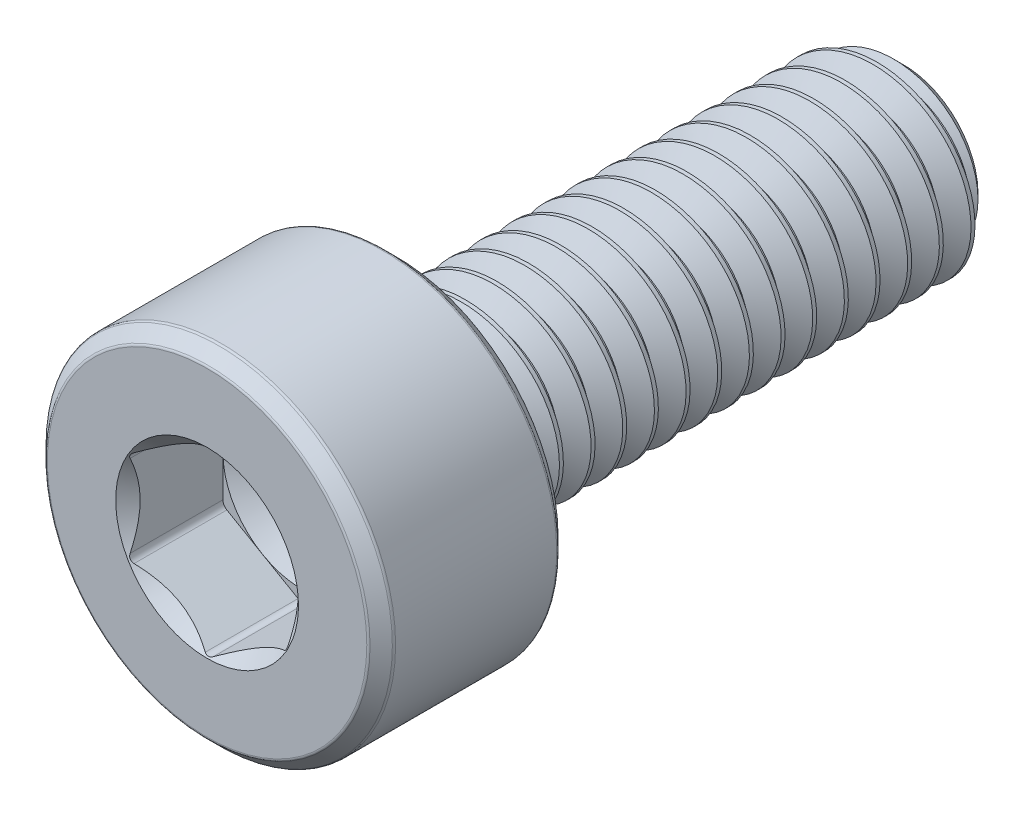
SolidWorks part; units mm, degrees
material "AISI 316 Stainless Steel Sheet (SS)"
ref_plane "Front Plane" through (0, 0, 0) normal (0, 0, 1) x (1, 0, 0)
ref_plane "Top Plane" through (0, 0, 0) normal (0, 1, 0) x (1, 0, 0)
ref_plane "Right Plane" through (0, 0, 0) normal (1, 0, 0) x (0, 0, -1)
sketch "Sketch1" plane through (0, 0, 0) normal (1, 0, 0) x (0, 0, -1)
  line L0 (-5.5, 0) -> (5.5, 0) construction
  line L1 (-5.5, 0) -> (-5.5, 2.75)
  line L2 (-5.5, 2.75) -> (-2.5, 2.75)
  line L3 (-2.5, 2.75) -> (-2.5, 1.5)
  line L4 (-2.5, 1.5) -> (5.1752, 1.5)
  line L5 (5.4687, 1.5541) -> (5.7187, 1.1211) construction
  line L6 (5.7187, 1.1211) -> (5.9687, 1.5541) construction
  line L7 (5.9687, 1.5541) -> (5.4687, 1.5541) construction
  line L8 (5.1752, 1.5) -> (5.5, 1.1752)
  line L9 (5.5, 1.1752) -> (5.5, 0)
  line L10 (5.5, 1.5) -> (5.9375, 1.5) construction
  line L11 (5.7187, 1.5541) -> (5.7187, 1.5) construction
  line L12 (5.7187, 1.5) -> (5.7187, 1.1752) construction
  line L13 (5.7187, 1.1752) -> (5.7187, 1.1211) construction
  line L14 (5.6875, 1.1752) -> (5.75, 1.1752)
  line L15 (5.4844, 1.5271) -> (5.9531, 1.5271)
  line L16 (5.75, 1.1752) -> (5.9531, 1.5271)
  line L17 (5.6875, 1.1752) -> (5.4844, 1.5271)
  line L18 (-5.5, 1.25) -> (-4, 1.25)
  line L19 (-4, 1.25) -> (-4, 0)
  line L20 (3.75, 1.5) -> (3.75, -1.5) construction
  point P20 (5.7187, 1.5271)
  point P22 (3.75, -1.5)
  point P28 (3.75, 0)
  point P29 (5.1752, -1.5)
  dimension "Head Diameter" = 5.5
  dimension "Length" = 8
  dimension "Head Height" = 3
  dimension "Thread Size" = 3
  dimension "D1" = 45
  dimension "Thread Pitch" = 0.5
  dimension "D3" = 0.0625
  dimension "Drive Size" = 2.5
  dimension "D4" = 1.75
  dimension "D5" = 1.5
sketch "Sketch3" plane through (0, 0, 0) normal (1, 0, 0) x (0, 0, -1)
  line L0 (-5.5, 2.5224) -> (-5.5, 1.25)
  line L1 (-5.5, 1.25) -> (-4, 1.25)
  line L2 (-4, 1.25) -> (-4, 0)
  line L3 (-4, 0) -> (5.5, 0)
  line L4 (5.5, 0) -> (5.5, 1.1752)
  line L5 (5.5, 1.1752) -> (5.1752, 1.5)
  line L6 (5.1752, 1.5) -> (-2.5, 1.5)
  line L7 (-2.5, 1.5) -> (-2.5, 2.5224)
  line L8 (-2.7276, 2.75) -> (-5.2724, 2.75)
  line L9 (-5.4849, 2.5589) -> (-5.3089, 2.7349)
  line L11 (-5.5, 2.75) -> (-2.5, 2.75) construction
  line L12 (-2.6911, 2.7349) -> (-2.5151, 2.5589)
  arc A5 (-2.5151, 2.5589) -> (-2.5, 2.5224) centre (-2.5516, 2.5224) cw
  arc A6 (-2.7276, 2.75) -> (-2.6911, 2.7349) centre (-2.7276, 2.6984) cw
  arc A7 (-5.2724, 2.75) -> (-5.3089, 2.7349) centre (-5.2724, 2.6984) ccw
  arc A8 (-5.5, 2.5224) -> (-5.4849, 2.5589) centre (-5.4484, 2.5224) cw
  point P17 (-4, 2.75)
  point P29 (-5.5, 2.5438)
  dimension "D3" = 0.0516
  dimension "D1" = 45
  dimension "D2" = 0.2062
revolve "Revolve1" add sketch "Sketch3" angle 360 about L0
sketch "Sketch4" plane through (0, 0, 5.5) normal (0, 0, 1) x (1, 0, 0)
  line L1 (0, 1.4434) -> (-1.25, 0.7217)
  line L2 (-1.25, 0.7217) -> (-1.25, -0.7217)
  line L3 (-1.25, -0.7217) -> (0, -1.4434)
  line L4 (0, -1.4434) -> (1.25, -0.7217)
  line L5 (1.25, -0.7217) -> (1.25, 0.7217)
  line L6 (1.25, 0.7217) -> (0, 1.4434)
  circle A0 centre (0, 0) radius 1.25 construction
extrude "Cut-Extrude1" cut sketch "Sketch4" against normal up to vertex (1.5 mm away) up to point (0, 1.25, 4)
sketch "Sketch5" plane through (0, 0, 5.5) normal (0, 0, 1) x (1, 0, 0)
  circle A0 centre (0, 0) radius 1.4434
extrude "Cut-Extrude2" cut sketch "Sketch5" against normal up to next (1.5 mm away) draft 45
sketch "Sketch10" plane through (0, 0, 4) normal (0, 0, 1) x (1, 0, 0)
  line L0 (1.25, 0.7217) -> (1.25, -0.7217) construction
  circle A0 centre (0, 0) radius 1.25
extrude "Cut-Extrude3" cut sketch "Sketch10" against normal through all draft 60
fillet "Fillet1" radius 0.125 6 edges at (-1.25, 0.7217, 4.75) (0, 1.4434, 4.75) (1.25, 0.7217, 4.75) (1.25, -0.7217, 4.75) (0, -1.4434, 4.75) (-1.25, -0.7217, 4.75)
sketch "Sketch6" plane through (0, 0, -5.5) normal (0, 0, -1) x (-1, 0, 0)
  circle A0 centre (0, 0) radius 1.5 construction
  circle A1 centre (0, 0) radius 1.5
curve "Helix/Spiral1" pitch 0.5 height 8.5 radius 1.5 centre (0, 0, -5.5) axis (0, 0, 1) start towards (0, 1, 0)
sketch "Sketch7" plane through (0, 0, 0) normal (1, 0, 0) x (0, 0, -1)
  line L0 (5.6875, 1.1752) -> (5.75, 1.1752) construction
  line L1 (5.6875, 1.1752) -> (5.4844, 1.5271) construction
  line L2 (5.4844, 1.5271) -> (5.9531, 1.5271) construction
  line L3 (5.75, 1.1752) -> (5.9531, 1.5271) construction
  line L4 (5.6875, 1.1752) -> (5.75, 1.1752)
  line L5 (5.6875, 1.1752) -> (5.4844, 1.5271)
  line L6 (5.4844, 1.5271) -> (5.9531, 1.5271)
  line L7 (5.75, 1.1752) -> (5.9531, 1.5271)
sweep "Cut-Sweep1" cut profiles "Sketch7" path "Helix/Spiral1" align with end faces yes
sketch "Sketch11" plane through (0, 0, 0) normal (1, 0, 0) x (0, 0, -1)
  line L0 (-2.5, 1.625) -> (-2.375, 1.5) construction
  line L1 (-2.5, 2.75) -> (-2.5, 1.5) construction
  line L2 (-2.5, 1.5) -> (5.1752, 1.5) construction
  line L3 (-2.375, 1.5) -> (-2.25, 1.5)
  line L4 (-2.25, 1.5) -> (-0.75, 0)
  line L5 (-5.5, 0) -> (5.5, 0) construction
  line L6 (-0.75, 0) -> (-2.5, 0)
  line L7 (-2.5, 0) -> (-2.5, 1.625) construction
  line L8 (-2.5, 1.625) -> (-3.2783, 1.625)
  line L9 (-3.2783, 1.625) -> (-3.2783, 0)
  line L10 (-3.2783, 0) -> (-2.5, 0)
  arc A0 (-2.375, 1.5) -> (-2.5, 1.625) centre (-2.375, 1.625) cw
  dimension "D1" = 45
  dimension "D2" = 0.125
  dimension "D3" = 45
  dimension "D4" = 0.25
revolve "Revolve2" add sketch "Sketch11" angle 360 about L6
equation "\"D3@Sketch1\" = \"Thread Pitch@Sketch1\" / 8"
equation "\"D4@Sketch1\" = \"Thread Pitch@Sketch1\" * 3.5"
equation "\"D3@Helix/Spiral1\" = \"Length@Sketch1\" + \"Thread Pitch@Sketch1\""
equation "\"D4@Helix/Spiral1\" = \"Thread Pitch@Sketch1\""
equation "\"D5@Sketch1\"=\"Head Height@Sketch1\"*0.5"
equation "\"D2@Sketch3\"=\"Head Diameter@Sketch1\" *0.0375"
equation "\"D2@Sketch11\"=\"Thread Pitch@Sketch1\" / 4"
equation "\"D4@Sketch11\"=\"Thread Pitch@Sketch1\"/2"
equation "\"D1@Fillet1\"=\"Drive Size@Sketch1\"*0.05"
equation "\"D1@Fillet1\" = \"Drive Size@Sketch1\" * 0.05"
equation "\"D3@Sketch3\"=\"D2@Sketch3\"*0.25"
